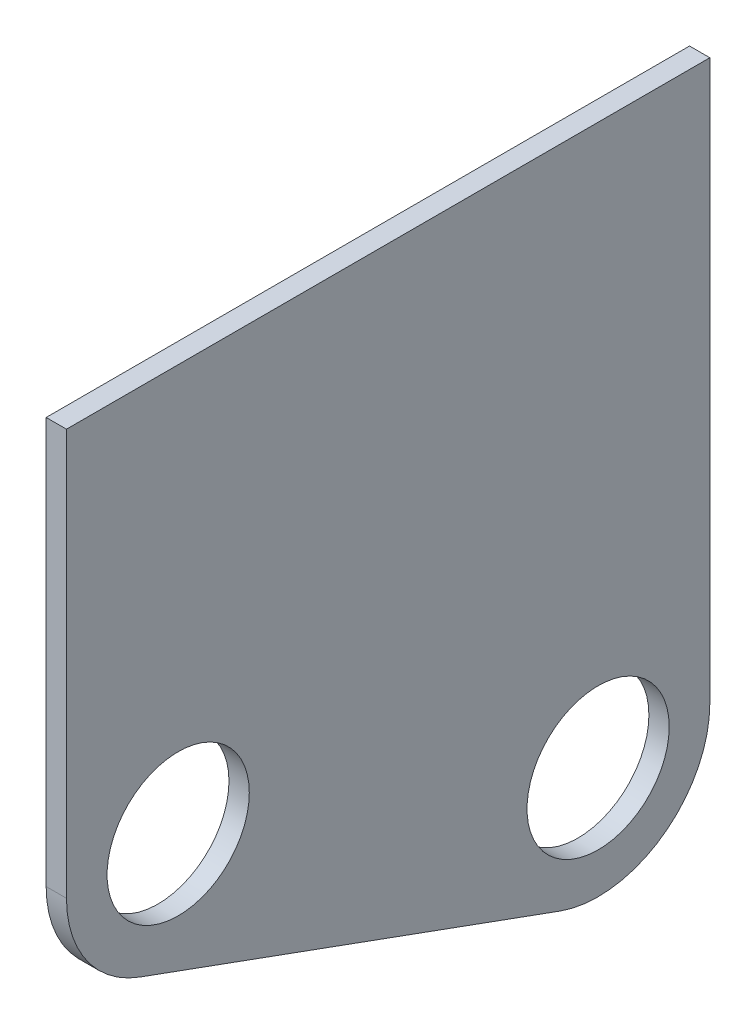
SolidWorks part; units mm, degrees
material "6061-T6 (SS)"
ref_plane "Front" through (0, 0, 0) normal (0, 0, 1) x (1, 0, 0)
ref_plane "Top" through (0, 0, 0) normal (0, 1, 0) x (1, 0, 0)
ref_plane "Right" through (0, 0, 0) normal (1, 0, 0) x (0, 0, -1)
sketch "Sketch2" plane through (0, 0, 0) normal (1, 0, 0) x (0, 0, -1)
  line L0 (50.2813, 0) -> (-50.2813, 0)
  line L1 (-50.2813, 0) -> (-50.2813, -63.5)
  line L2 (-38.7913, -79.9094) -> (26.8462, -103.7995)
  line L3 (50.2813, -87.3901) -> (50.2813, 0)
  circle A0 centre (-32.8188, -63.5) radius 11.1125
  circle A1 centre (32.8188, -87.3901) radius 11.1125
  circle A2 centre (-32.8188, -63.5) radius 19.05 construction
  circle A3 centre (32.8188, -87.3901) radius 12.7 construction
  arc A4 (-50.2813, -63.5) -> (-38.7913, -79.9094) centre (-32.8188, -63.5) ccw
  arc A5 (26.8462, -103.7995) -> (50.2813, -87.3901) centre (32.8188, -87.3901) ccw
  point P4 (0, 0)
  dimension "D1" = 22.225
  dimension "D2" = 38.1
  dimension "D3" = 25.4
  dimension "D4" = 38.1
  dimension "D5" = 6.35
  dimension "D6" = 6.35
  dimension "D7" = 110
  dimension "D8" = 63.5
extrude "Boss-Extrude1" add sketch "Sketch2" along normal blind 3.175
